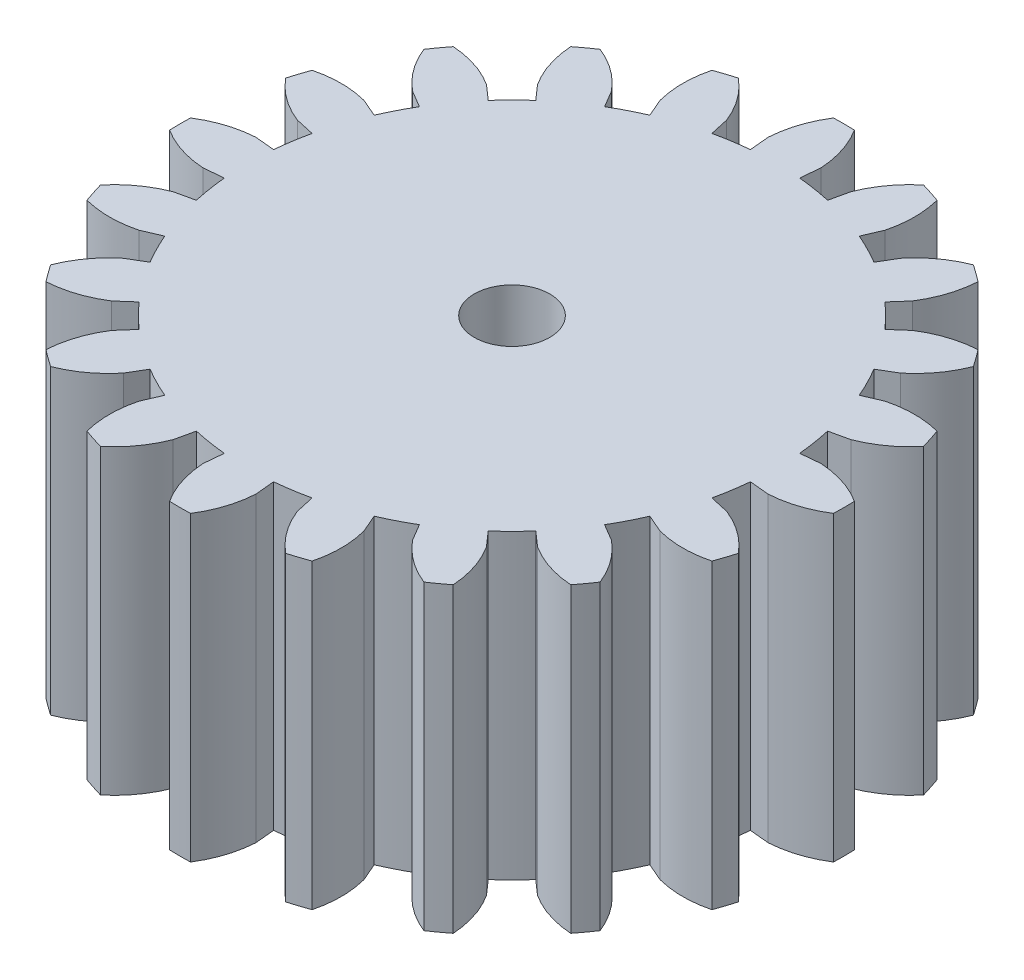
SolidWorks part; units mm, degrees
ref_plane "Спереди" through (0, 0, 0) normal (0, 0, 1) x (1, 0, 0)
ref_plane "Сверху" through (0, 0, 0) normal (0, 1, 0) x (1, 0, 0)
ref_plane "Справа" through (0, 0, 0) normal (1, 0, 0) x (0, 0, -1)
other "Configuration Table"
sketch "Эскиз1" plane through (0, 0, 0) normal (0, 1, 0) x (1, 0, 0)
  circle A0 centre (0, 0) radius 17.5
  dimension "D1" = 35
extrude "Бобышка-Вытянуть1" add sketch "Эскиз1" along normal blind 20
sketch "Эскиз2" plane through (0, 0, 0) normal (0, -1, 0) x (1, 0, 0)
  line L0 (0, 0) -> (0, 22) construction
  line L1 (0, 0) -> (-1.7523, 18.712) construction
  line L2 (0, 0) -> (1.7523, 18.712) construction
  line L5 (-1.5692, 19.9383) -> (0, 0) construction
  line L6 (0, 0) -> (1.5692, 19.9383) construction
  line L7 (-0.6949, 21.989) -> (0, 0) construction
  line L8 (-1.6317, 17.4238) -> (-1.7523, 18.712)
  line L9 (1.7523, 18.712) -> (1.6317, 17.4238)
  circle A0 centre (0, 0) radius 18.7938 construction
  circle A1 centre (0, 0) radius 20 construction
  circle A2 centre (0, 0) radius 22 construction
  arc A3 (-0.6949, 21.989) -> (0.6949, 21.989) centre (0, 0) cw
  arc A4 (-1.6317, 17.4238) -> (1.6317, 17.4238) centre (0, 0) cw
  circle A5 centre (0, 0) radius 17.5 construction
  arc A6 (-1.5692, 19.9383) -> (1.5692, 19.9383) centre (0, 0) cw construction
  arc A7 (-1.7523, 18.712) -> (-0.6949, 21.989) centre (5.0681, 18.3203) cw
  arc A8 (0.6949, 21.989) -> (1.7523, 18.712) centre (-5.0681, 18.3203) cw
  point P12 (0, 20)
  point P16 (0, 22)
  point P20 (0, 0)
  point P22 (0, 17.5)
  dimension "D1" = 37.5877
  dimension "D2" = 40
  dimension "D3" = 44
  dimension "D4" = 5.35
  dimension "D5" = 4.5
  dimension "D6" = 1.81
extrude "Бобышка-Вытянуть2" add sketch "Эскиз2" against normal blind 20
pattern_circular "Круговой массив1" count 20 over 360 about axis through (0, 20, 0) along (0, -1, 0) of "Бобышка-Вытянуть2" reverse direction yes
sketch "Эскиз3" plane through (0, 0, 0) normal (0, -1, 0) x (1, 0, 0)
  circle A0 centre (0, 0) radius 2.5
  dimension "D1" = 5
extrude "Вырез-Вытянуть1" cut sketch "Эскиз3" against normal through all
equation "\"Ширина груза\"= 420"
equation "\"Глубина груза\"= 490"
equation "\"Высота груза\"= 297"
equation "\"Ширина ячейки\"= \"Ширина груза\" + 10"
equation "\"Глубина ячейки\"= \"Глубина груза\" + 10"
equation "\"Высота ячейки\"= \"Высота груза\" + 10 + 13"
equation "\"Колво ячеек ширина\"= 2"
equation "\"Колво ячеек высота\"= 2"
equation "\"Толщина стенки\"= 10"
equation "\"Крепление дверцы\"= 5"
equation "\"Ширина рейки\"= \"Толщина шестерни\""
equation "\"Высота рейки\"= 20"
equation "\"Высота пола\"= 20"
equation "\"Колво полозьев\"= 5"
equation "\"Отступ рейки\"= 20"
equation "\"Глубина каретки\"= \"Глубина ячейки\" + 80"
equation "\"Длинна рейки\"= ( \"Ширина ячейки\" + \"Толщина стенки\" + \"Крепление дверцы\" ) * \"Колво ячеек ширина\" + \"Ширина ячейки выгрузки\" * \"Колво выгрузки\" + \"Толщина стенки\""
equation "\"Отступ шпильки\"= 20"
equation "\"Диаметр шпильки\"= 5"
equation "\"Длинна шпильки\"= ( \"Высота ячейки\" + \"Толщина стенки\" + \"Высота пола\" ) * \"Колво ячеек высота\" + ( \"Толщина стенки\" + \"Отступ рейки\" ) * 2"
equation "\"Ширина пластины\"= 50  "
equation "\"Высота зона выгрузки\"= \"Высота ячейки\" * 2 + \"Толщина стенки\" * 2"
equation "\"Колво выгрузки\"= 1"
equation "\"Ширина ячейки выгрузки\"= \"Ширина ячейки\" + \"Толщина стенки\" + \"Отступ крепления мотора фиксации\"*2"
equation "\"Отступ крепления мотора фиксации\" = 30"
equation "\"Мотор X ширина корпуса\"= 42.3"
equation "\"Мотор X высота корпуса\"= 42.3"
equation "\"Мотор X длина корпуса\"= 40"
equation "\"Мотор X вылет вала\"= 19.8"
equation "\"Мотор Y ширина корпуса\"= 42.3"
equation "\"Мотор Y высота корпуса\"= 42.3"
equation "\"Мотор Y длина корпуса\"= 48"
equation "\"Мотор Y вылет вала\"= 30"
equation "\"Мотор Z ширина корпуса\"= 42"
equation "\"Мотор Z высота корпуса\"= 42"
equation "\"Мотор Z длина корпуса\"= 40"
equation "\"Мотор Z вылет вала\"= 23"
equation "\"Мотор диаметр вала ПРЕДВ\"= 5"
equation "\"Мотор шаг крепления ПРЕДВ\"= 31"
equation "\"Мотор диаметр отверстий ПРЕДВ\"= 3"
equation "\"Мотор глубина отверстий ПРЕДВ\"= 4.5"
equation "\"Мотор диаметр буртика ПРЕДВ\"= 22"
equation "\"Мотор высота буртика ПРЕДВ\"= 2"
equation "\"Мотор диаметр шкива ПРЕДВ\"= 16"
equation "\"Мотор длина шкива ПРЕДВ\"= 12"
equation "\"Мотор отступ шкива ПРЕДВ\"= 5"
equation "\"Мотор X шаг градусов\"= 1.8"
equation "\"Мотор Y шаг градусов\"= 1.8"
equation "\"Мотор Z шаг градусов\"= 1.8"
equation "\"Мотор Y диаметр ротора\"= 25.78"
equation "\"Толщина шестерни\" = 20"
equation "\"D1@Бобышка-Вытянуть1\"=\"Толщина шестерни\""
equation "\"D1@Бобышка-Вытянуть2\"=\"Толщина шестерни\""
equation "\"D1@Эскиз3\"=\"Мотор диаметр вала ПРЕДВ\""
